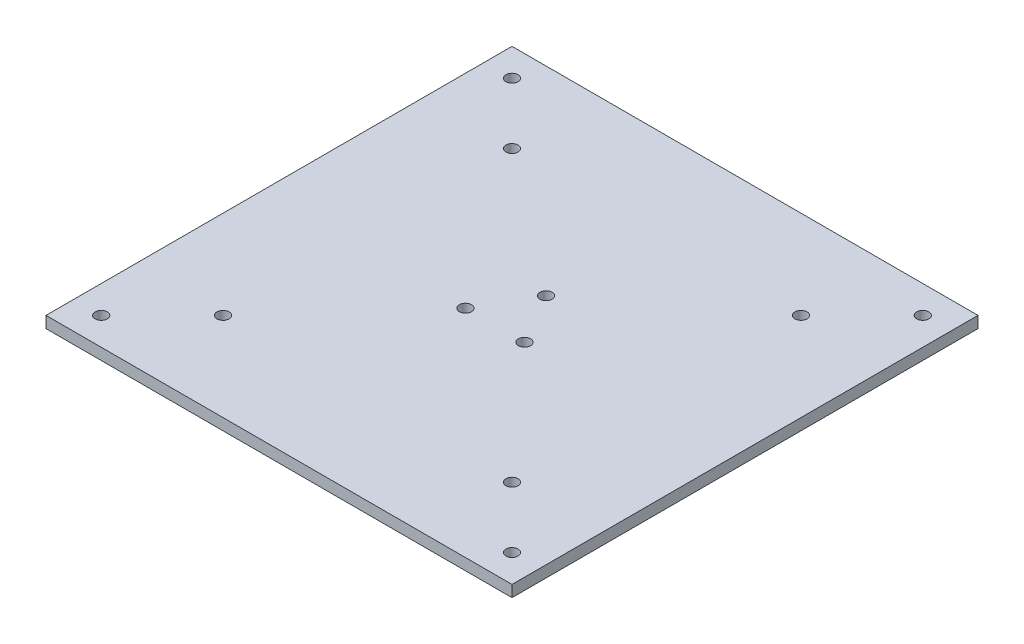
SolidWorks part; units mm, degrees
ref_plane "Front Plane" through (0, 0, 0) normal (0, 0, 1) x (1, 0, 0)
ref_plane "Top Plane" through (0, 0, 0) normal (0, 1, 0) x (1, 0, 0)
ref_plane "Right Plane" through (0, 0, 0) normal (1, 0, 0) x (0, 0, -1)
sketch "Sketch2" plane through (0, 0, 0) normal (0, 1, 0) x (1, 0, 0)
  line L1 (-65, -65) -> (65, -65)
  line L2 (-65, -65) -> (-65, 65)
  line L3 (-65, 65) -> (65, 65)
  line L4 (65, -65) -> (65, 65)
  line L5 (-65, -65) -> (65, 65) construction
  line L6 (-65, 65) -> (65, -65) construction
  point P0 (0, 0)
  dimension "D1" = 130
  dimension "D2" = 130
extrude "Boss-Extrude1" add sketch "Sketch2" along normal blind 3.2
sketch "Sketch4" plane through (0, 3.2, 0) normal (0, 1, 0) x (1, 0, 0)
  line L8 (57.3, -57.3) -> (57.3, 57.3)
  line L9 (57.3, 57.3) -> (-57.3, 57.3)
  line L10 (-57.3, 57.3) -> (-57.3, -57.3)
  line L11 (-57.3, -57.3) -> (57.3, -57.3)
  line L12 (57.3, -57.3) -> (57.3, 57.3) construction
  line L13 (57.3, 57.3) -> (-57.3, 57.3) construction
  line L14 (-57.3, 57.3) -> (-57.3, -57.3) construction
  line L15 (-57.3, -57.3) -> (57.3, -57.3) construction
  circle A0 centre (-57.3, 57.3) radius 1.7
  circle A1 centre (57.3, 57.3) radius 1.7
  circle A2 centre (57.3, -57.3) radius 1.7
  circle A3 centre (-57.3, -57.3) radius 1.7
  dimension "D2" = 3.4
  dimension "D1" = 7.7
extrude "Cut-Extrude1" cut sketch "Sketch4" against normal up to next
sketch "Sketch6" plane through (0, 3.2, 0) normal (0, 1, 0) x (1, 0, 0)
  line L6 (-40.3051, -40.3051) -> (40.3051, -40.3051) construction
  line L7 (-40.3051, -40.3051) -> (-40.3051, 40.3051) construction
  line L8 (-40.3051, 40.3051) -> (40.3051, 40.3051) construction
  line L9 (40.3051, -40.3051) -> (40.3051, 40.3051) construction
  line L10 (-40.3051, -40.3051) -> (40.3051, 40.3051) construction
  line L11 (-40.3051, 40.3051) -> (40.3051, -40.3051) construction
  circle A4 centre (-40.3051, 40.3051) radius 1.7
  circle A5 centre (40.3051, 40.3051) radius 1.7
  circle A6 centre (40.3051, -40.3051) radius 1.7
  circle A7 centre (-40.3051, -40.3051) radius 1.7
  point P0 (0, 0)
  dimension "D2" = 3.4
  dimension "D1" = 57
extrude "Cut-Extrude2" cut sketch "Sketch6" against normal up to next
sketch "Sketch7" plane through (0, 0, 0) normal (0, -1, 0) x (1, 0, 0)
  line L24 (40.3051, 37.1528) -> (43.0351, 38.7289)
  line L28 (-37.1528, 40.3051) -> (-38.7289, 43.0351)
  line L29 (-38.7289, 43.0351) -> (-41.8813, 43.0351)
  line L30 (-41.8813, 43.0351) -> (-43.4574, 40.3051)
  line L31 (-43.4574, 40.3051) -> (-41.8813, 37.5751)
  line L32 (-41.8813, 37.5751) -> (-38.7289, 37.5751)
  line L33 (-38.7289, 37.5751) -> (-37.1528, 40.3051)
  line L34 (43.0351, 38.7289) -> (43.0351, 41.8813)
  line L35 (43.0351, 41.8813) -> (40.3051, 43.4574)
  line L36 (40.3051, 43.4574) -> (37.5751, 41.8813)
  line L37 (37.5751, 41.8813) -> (37.5751, 38.7289)
  line L38 (37.5751, 38.7289) -> (40.3051, 37.1528)
  line L39 (37.1528, -40.3051) -> (38.7289, -43.0351)
  line L40 (38.7289, -43.0351) -> (41.8813, -43.0351)
  line L41 (41.8813, -43.0351) -> (43.4574, -40.3051)
  line L42 (43.4574, -40.3051) -> (41.8813, -37.5751)
  line L43 (41.8813, -37.5751) -> (38.7289, -37.5751)
  line L44 (38.7289, -37.5751) -> (37.1528, -40.3051)
  line L45 (-40.3051, -37.1528) -> (-43.0351, -38.7289)
  line L46 (-43.0351, -38.7289) -> (-43.0351, -41.8813)
  line L47 (-43.0351, -41.8813) -> (-40.3051, -43.4574)
  line L48 (-40.3051, -43.4574) -> (-37.5751, -41.8813)
  line L49 (-37.5751, -41.8813) -> (-37.5751, -38.7289)
  line L50 (-37.5751, -38.7289) -> (-40.3051, -37.1528)
  circle A0 centre (-40.3051, 40.3051) radius 2.73 construction
  circle A2 centre (-40.3051, 40.3051) radius 4.25
  circle A3 centre (40.3051, 40.3051) radius 4.25
  circle A4 centre (40.3051, -40.3051) radius 4.25
  circle A5 centre (-40.3051, -40.3051) radius 4.25
  point P30 (0, 0)
  dimension "D1" = 5.46
  dimension "D3" = 4
  dimension "D2" = 8.5
extrude "Boss-Extrude3" add sketch "Sketch7" along normal blind 3.5
fillet "Fillet3" radius 1.5 4 edges at (40.3051, 0, -44.5551) (40.3051, 0, 36.0551) (-40.3051, 0, 36.0551) (-40.3051, 0, -44.5551)
fillet "Fillet4" radius 0.8 24 edges at (-43.0351, -3.5, -40.3051) (-38.9401, -3.5, -42.6693) (-37.5751, -3.5, -40.3051) (-38.9401, -3.5, -37.9408) (-41.6701, -3.5, -37.9408) (-41.6701, -3.5, -42.6693) (42.6693, -3.5, -41.6701) (42.6693, -3.5, -38.9401) (40.3051, -3.5, -37.5751) (37.9408, -3.5, -38.9401) (37.9408, -3.5, -41.6701) (40.3051, -3.5, -43.0351) (43.0351, -3.5, 40.3051) (41.6701, -3.5, 42.6693) (38.9401, -3.5, 42.6693) (37.5751, -3.5, 40.3051) (38.9401, -3.5, 37.9408) (41.6701, -3.5, 37.9408) (-40.3051, -3.5, 43.0351) (-42.6693, -3.5, 41.6701) (-42.6693, -3.5, 38.9401) (-37.9408, -3.5, 38.9401) (-37.9408, -3.5, 41.6701) (-40.3051, -3.5, 37.5751)
sketch "Sketch8" plane through (0, 3.2, 0) normal (0, 1, 0) x (1, 0, 0)
  circle A4 centre (0, 9.5) radius 1.7
  circle A5 centre (8.2272, -4.75) radius 1.7
  circle A6 centre (-8.2272, -4.75) radius 1.7
  point P9 (0, 0)
  dimension "D1" = 9.5
  dimension "D3" = 3.4
  dimension "D2" = 3
extrude "Cut-Extrude3" cut sketch "Sketch8" against normal up to next
equation "\"D1@Sketch4\"=4.50+3.2"
